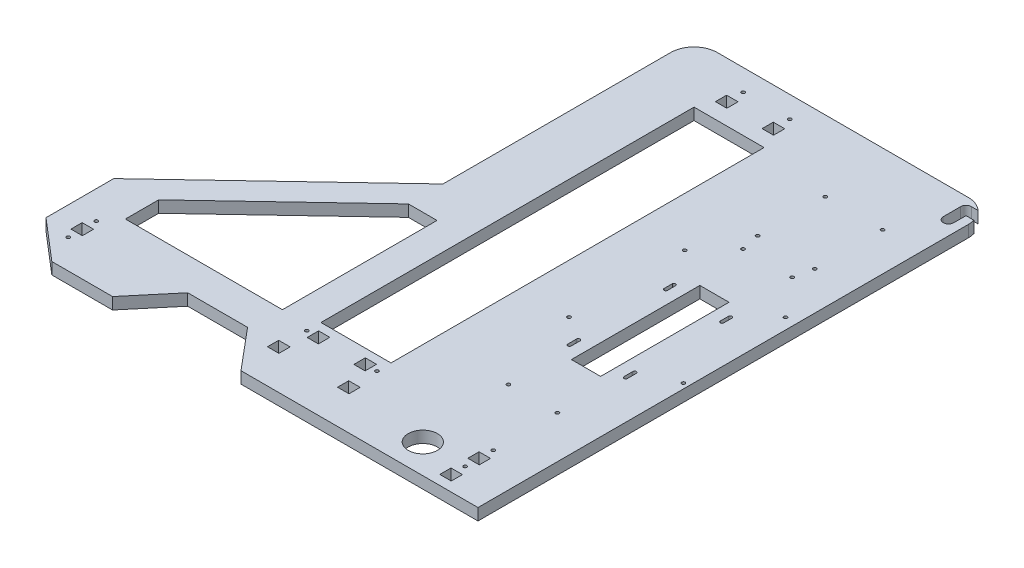
SolidWorks part; units mm, degrees
ref_plane "Front Plane" through (0, 0, 0) normal (0, 0, 1) x (1, 0, 0)
ref_plane "Top Plane" through (0, 0, 0) normal (0, 1, 0) x (1, 0, 0)
ref_plane "Right Plane" through (0, 0, 0) normal (1, 0, 0) x (0, 0, -1)
sketch "Sketch1" plane through (0, 0, 0) normal (0, 1, 0) x (1, 0, 0)
  line L0 (0, 0) -> (-235, 0)
  line L1 (-235, 0) -> (-235, -215)
  line L2 (-235, -215) -> (-380, -352)
  line L3 (-380, -352) -> (-380, -410)
  line L4 (-380, -410) -> (-345, -440)
  line L5 (-345, -440) -> (-293, -440)
  line L6 (-293, -440) -> (-263.6315, -405)
  line L7 (-263.6315, -405) -> (-212.3685, -405)
  line L8 (-212.3685, -405) -> (-183, -440)
  line L9 (-183, -440) -> (0, -440)
  line L10 (0, 0) -> (0, -440)
  line L12 (-293, -440) -> (-183, -440) construction
  dimension "D3" = 235
  dimension "D5" = 58
  dimension "D13" = 190
  dimension "D7" = 35
  dimension "D15" = 52
  dimension "D12" = 30
  dimension "D10" = 35
  dimension "D6" = 380
  dimension "D4" = 440
  dimension "D2" = 50
  dimension "D8" = 50
  dimension "D9" = 110
extrude "Boss-Extrude1" add sketch "Sketch1" along normal blind 10
sketch "Sketch16" plane through (0, 10, 0) normal (0, 1, 0) x (1, 0, 0)
  line L0 (0, -440) -> (20, -440)
  line L1 (20, -440) -> (20, 0)
  line L2 (20, 0) -> (0, 0)
  line L3 (0, 0) -> (0, -440)
  dimension "D1" = 20
  dimension "D2" = 90
extrude "Boss-Extrude2" add sketch "Sketch16" against normal through all
sketch "Sketch2" plane through (0, 10, 0) normal (0, 1, 0) x (1, 0, 0)
  line L0 (-235, -215) -> (-235, -405) construction
  line L1 (-263.6315, -405) -> (-212.3685, -405) construction
  line L2 (-345, -440) -> (-345, -318.931) construction
  line L3 (-235, -215) -> (-380, -352) construction
  line L4 (-345, -348.5097) -> (-235, -244.5787)
  line L5 (-235, -244.5787) -> (-210.5, -244.5787)
  line L6 (-210.5, -244.5787) -> (-210.5, -377)
  line L7 (-210.5, -377) -> (-345, -377)
  line L8 (-345, -377) -> (-345, -348.5097)
  line L9 (0, -440) -> (0, 0) construction
  line L10 (-184.5, -370) -> (-124.5, -370)
  line L11 (-184.5, -370) -> (-184.5, -50.45)
  line L12 (-184.5, -50.45) -> (-124.5, -50.45)
  line L13 (-124.5, -370) -> (-124.5, -50.45)
  line L14 (-124.5, -382.1) -> (-184.5, -382.1) construction
  line L15 (-16, -440) -> (-16, 0) construction
  line L16 (20, 0) -> (-235, 0) construction
  line L17 (-355.95, -430.6143) -> (-355.95, -329.2769) construction
  line L18 (-20.9, -431.8) -> (-11.1, -431.8)
  line L19 (-20.9, -431.8) -> (-20.9, -422.2)
  line L20 (-20.9, -422.2) -> (-11.1, -422.2)
  line L21 (-11.1, -431.8) -> (-11.1, -422.2)
  line L22 (-20.9, -431.8) -> (-11.1, -422.2) construction
  line L23 (-20.9, -422.2) -> (-11.1, -431.8) construction
  line L24 (-20.9, -407.8) -> (-11.1, -407.8)
  line L25 (-20.9, -407.8) -> (-20.9, -398.2)
  line L26 (-20.9, -398.2) -> (-11.1, -398.2)
  line L27 (-11.1, -407.8) -> (-11.1, -398.2)
  line L28 (-20.9, -407.8) -> (-11.1, -398.2) construction
  line L29 (-20.9, -398.2) -> (-11.1, -407.8) construction
  line L30 (-380, -410) -> (-345, -440) construction
  line L32 (-351.05, -398.2) -> (-360.85, -398.2)
  line L33 (-351.05, -398.2) -> (-351.05, -407.8)
  line L34 (-351.05, -407.8) -> (-360.85, -407.8)
  line L35 (-360.85, -398.2) -> (-360.85, -407.8)
  line L36 (-351.05, -398.2) -> (-360.85, -407.8) construction
  line L37 (-351.05, -407.8) -> (-360.85, -398.2) construction
  line L38 (-183, -440) -> (20, -440) construction
  line L39 (-183, -440) -> (20, -440) construction
  line L40 (-173.724, -32.45) -> (-113.724, -32.45) construction
  line L41 (-154.5, -50.45) -> (-154.5, -32.45) construction
  line L42 (-179.4, -27.65) -> (-169.6, -27.65)
  line L43 (-179.4, -27.65) -> (-179.4, -37.25)
  line L44 (-179.4, -37.25) -> (-169.6, -37.25)
  line L45 (-169.6, -27.65) -> (-169.6, -37.25)
  line L46 (-179.4, -27.65) -> (-169.6, -37.25) construction
  line L47 (-179.4, -37.25) -> (-169.6, -27.65) construction
  line L48 (-129.6, -37.25) -> (-139.4, -27.65) construction
  line L49 (-129.6, -27.65) -> (-139.4, -37.25) construction
  line L50 (-139.4, -27.65) -> (-139.4, -37.25)
  line L51 (-129.6, -37.25) -> (-139.4, -37.25)
  line L52 (-129.6, -27.65) -> (-129.6, -37.25)
  line L53 (-129.6, -27.65) -> (-139.4, -27.65)
  line L54 (-174.5, -32.45) -> (-174.5, -18.45) construction
  line L55 (-134.5, -32.45) -> (-134.5, -18.45) construction
  line L56 (-154.5, -370) -> (-154.5, -440) construction
  line L57 (-174.5, -382.1) -> (-134.5, -382.1) construction
  line L58 (-129.7, -387) -> (-139.3, -377.2) construction
  line L59 (-179.3, -377.2) -> (-169.7, -377.2)
  line L60 (-179.3, -377.2) -> (-179.3, -387)
  line L61 (-179.3, -387) -> (-169.7, -387)
  line L62 (-169.7, -377.2) -> (-169.7, -387)
  line L63 (-179.3, -377.2) -> (-169.7, -387) construction
  line L64 (-179.3, -387) -> (-169.7, -377.2) construction
  line L65 (-129.7, -377.2) -> (-139.3, -387) construction
  line L66 (-139.3, -377.2) -> (-139.3, -387)
  line L67 (-129.7, -387) -> (-139.3, -387)
  line L68 (-129.7, -377.2) -> (-129.7, -387)
  line L69 (-129.7, -377.2) -> (-139.3, -377.2)
  line L70 (-119.6, -410.9) -> (-129.4, -401.3) construction
  line L71 (-189.4, -401.3) -> (-179.6, -401.3)
  line L72 (-189.4, -401.3) -> (-189.4, -410.9)
  line L73 (-189.4, -410.9) -> (-179.6, -410.9)
  line L74 (-179.6, -401.3) -> (-179.6, -410.9)
  line L75 (-189.4, -401.3) -> (-179.6, -410.9) construction
  line L76 (-189.4, -410.9) -> (-179.6, -401.3) construction
  line L77 (-119.6, -401.3) -> (-129.4, -410.9) construction
  line L78 (-129.4, -401.3) -> (-129.4, -410.9)
  line L79 (-119.6, -410.9) -> (-129.4, -410.9)
  line L80 (-119.6, -401.3) -> (-119.6, -410.9)
  line L81 (-119.6, -401.3) -> (-129.4, -401.3)
  line L82 (-360.85, -398.2) -> (-11.1, -398.2) construction
  circle A0 centre (-16, -415) radius 1.45
  circle A1 centre (-16, -391) radius 1.45
  circle A2 centre (-355.95, -415) radius 1.45
  circle A3 centre (-355.95, -391) radius 1.45
  circle A4 centre (-174.5, -18.45) radius 1.45
  circle A5 centre (-134.5, -18.45) radius 1.45
  circle A6 centre (-124.5, -382.1) radius 1.45
  circle A7 centre (-184.5, -382.1) radius 1.45
  point P25 (-16, -427)
  point P30 (-16, -403)
  point P44 (-355.95, -403)
  point P61 (-174.5, -32.45)
  point P72 (-134.5, -32.45)
  point P85 (-174.5, -382.1)
  point P94 (-134.5, -382.1)
  point P95 (-184.5, -406.1)
  point P104 (-124.5, -406.1)
  point P105 (-154.5, -382.1)
  dimension "D13" = 2.9
  dimension "D14" = 2.9
  dimension "D23" = 2.9
  dimension "D24" = 2.9
  dimension "D31" = 2.9
  dimension "D37" = 2.9
  dimension "D1" = 21.5
  dimension "D2" = 28
  dimension "D3" = 24.5
  dimension "D4" = 60
  dimension "D7" = 26
  dimension "D8" = 9.6
  dimension "D9" = 9.8
  dimension "D10" = 9.8
  dimension "D11" = 9.6
  dimension "D12" = 24
  dimension "D15" = 24
  dimension "D19" = 9.8
  dimension "D20" = 9.6
  dimension "D26" = 12
  dimension "D27" = 9.8
  dimension "D28" = 9.6
  dimension "D33" = 9.6
  dimension "D38" = 9.8
  dimension "D39" = 9.6
  dimension "D41" = 24
  dimension "D34" = 30
  dimension "D36" = 12.1
  dimension "D30" = 18
  dimension "D29" = 40
  dimension "D17" = 13
  dimension "D32" = 14
  dimension "D35" = 20
  dimension "D16" = 12
  dimension "D21" = 90
  dimension "D25" = 24
  dimension "D5" = 349.75
  dimension "D22" = 349.75
  dimension "D40" = 30
  dimension "D6" = 70
  dimension "D42" = 0
  dimension "D43" = 0
  dimension "D18" = 16
  dimension "D44" = 9.8
extrude "Cut-Extrude1" cut sketch "Sketch2" against normal through all
fillet "Fillet1" radius 20 2 edges at (-235, 5, 0) (20, 5, 0)
sketch "Sketch11" plane through (0, 10, 0) normal (0, 1, 0) x (1, 0, 0)
  line L0 (-124.5, -210.225) -> (20, -210.225) construction
  line L1 (20, -440) -> (20, -20) construction
  line L3 (-52.25, -210.225) -> (-52.25, -440) construction
  line L6 (-124.5, -370) -> (-124.5, -50.45) construction
  line L8 (-183, -440) -> (20, -440) construction
  circle A0 centre (-52.25, -415) radius 12.5
  circle A1 centre (-16, -415) radius 1.45 construction
  dimension "D1" = 25
  dimension "D2" = 0
  dimension "D3" = 0
extrude "WiringHole" cut sketch "Sketch11" against normal through all
sketch "Sketch9" [suppressed] plane through (0, 10, 0) normal (0, 1, 0) x (1, 0, 0)
  line L0 (-52.25, -402.5) -> (-52.25, 0) construction
  line L1 (0, 0) -> (-215, 0) construction
  line L2 (-124.5, -205.225) -> (20, -205.225) construction
  line L3 (-124.5, -365) -> (-124.5, -45.45) construction
  line L4 (-4.75, -116.725) -> (-4.75, -293.725) construction
  line L6 (-99.75, -116.725) -> (-4.75, -116.725) construction
  line L7 (-4.75, -293.725) -> (-99.75, -293.725) construction
  line L8 (-99.75, -293.725) -> (-99.75, -116.725) construction
  line L9 (20, -440) -> (20, -20) construction
  circle A0 centre (-52.25, -415) radius 12.5 construction
  circle A1 centre (-99.75, -116.725) radius 1.45
  circle A2 centre (-4.75, -116.725) radius 1.45
  circle A3 centre (-4.75, -293.725) radius 1.45
  circle A4 centre (-99.75, -293.725) radius 1.45
  dimension "D3" = 2.9
  dimension "D4" = 2.9
  dimension "D1" = 95
  dimension "D2" = 177
  dimension "D5" = 47.5
extrude "MountingHoles-PSU" [suppressed] cut sketch "Sketch9" against normal through all
sketch "Sketch10" plane through (0, 10, 0) normal (0, 1, 0) x (1, 0, 0)
  line L0 (-124.5, -210.225) -> (20, -210.225) construction
  line L1 (20, -440) -> (20, -20) construction
  line L2 (-49.75, -235.225) -> (-24.75, -235.225) construction
  line L3 (-37.25, -210.225) -> (-37.25, 0) construction
  line L4 (-52.25, -210.225) -> (-52.25, -184.5972) construction
  line L7 (-124.5, -370) -> (-124.5, -50.45) construction
  line L8 (-49.75, -290.225) -> (-24.75, -290.225)
  line L9 (-49.75, -290.225) -> (-49.75, -180.225)
  line L10 (-49.75, -180.225) -> (-24.75, -180.225)
  line L11 (-24.75, -290.225) -> (-24.75, -180.225)
  line L12 (-49.75, -290.225) -> (-24.75, -180.225) construction
  line L13 (-49.75, -180.225) -> (-24.75, -290.225) construction
  line L15 (0, 0) -> (-215, 0) construction
  line L17 (-37.25, -210.225) -> (-37.25, -440) construction
  line L18 (-183, -440) -> (20, -440) construction
  line L19 (-64.75, -210.225) -> (-39.75, -210.225) construction
  line L20 (-37.25, -290.225) -> (-37.25, -180.225) construction
  dimension "D1" = 25
  dimension "D2" = 110
  dimension "D3" = 0
  dimension "D4" = 0
  dimension "D5" = 0
  dimension "D6" = 25
  dimension "D7" = 15
extrude "WiringSlot" cut sketch "Sketch10" against normal through all
sketch "CenterLines" plane through (0, 10, 0) normal (0, 1, 0) x (1, 0, 0)
  line L0 (-37.25, -290.225) -> (-37.25, -180.225) construction
  line L1 (-49.75, -290.225) -> (-24.75, -290.225) construction
  line L2 (-24.75, -180.225) -> (-49.75, -180.225) construction
  line L3 (-49.75, -235.225) -> (-24.75, -235.225) construction
  line L4 (-49.75, -180.225) -> (-49.75, -290.225) construction
  line L5 (-24.75, -290.225) -> (-24.75, -180.225) construction
ref_plane "Plane1" through (-37.25, 0, 0) normal (1, 0, 0) x (0, 0, -1)
sketch "Sketch6" plane through (0, 10, 0) normal (0, 1, 0) x (1, 0, 0)
  line L0 (-37.25, -290.225) -> (-37.25, -180.225) construction
  line L1 (-61.35, -235.225) -> (-13.15, -235.225) construction
  line L2 (-13.15, -190.775) -> (-13.15, -273.275) construction
  line L3 (-49.75, -290.225) -> (-24.75, -290.225) construction
  line L4 (-49.75, -235.225) -> (-24.75, -235.225) construction
  line L5 (-24.75, -180.225) -> (-49.75, -180.225) construction
  line L6 (-13.15, -190.775) -> (-13.15, -197.775) construction
  line L7 (-11.7, -190.775) -> (-11.7, -197.775)
  line L8 (-14.6, -190.775) -> (-14.6, -197.775)
  line L9 (-49.75, -235.225) -> (-24.75, -235.225) construction
  line L10 (-49.75, -180.225) -> (-49.75, -290.225) construction
  line L11 (-24.75, -290.225) -> (-24.75, -180.225) construction
  line L12 (-13.15, -280.275) -> (-13.15, -273.275) construction
  line L13 (-14.6, -280.275) -> (-14.6, -273.275)
  line L14 (-61.35, -272.675) -> (-61.35, -197.775) construction
  line L15 (-13.15, -280.275) -> (-13.15, -197.775) construction
  line L16 (-11.7, -280.275) -> (-11.7, -273.275)
  arc A2 (-11.7, -190.775) -> (-14.6, -190.775) centre (-13.15, -190.775) ccw
  arc A3 (-14.6, -197.775) -> (-11.7, -197.775) centre (-13.15, -197.775) ccw
  circle A4 centre (-61.35, -272.675) radius 1.45
  circle A6 centre (-61.35, -197.775) radius 1.45
  arc A8 (-14.6, -280.275) -> (-11.7, -280.275) centre (-13.15, -280.275) ccw
  arc A9 (-11.7, -273.275) -> (-14.6, -273.275) centre (-13.15, -273.275) ccw
  point P20 (-13.15, -194.275)
  point P25 (-13.15, -276.775)
  dimension "D6" = 0
  dimension "D8" = 2.9
  dimension "D12" = 2.9
  dimension "D4" = 1.45
  dimension "D5" = 1.45
  dimension "D11" = 82.5
  dimension "D14" = 74.9
  dimension "D2" = 24.1
  dimension "D3" = 48.2
  dimension "D9" = 7
  dimension "D10" = 7
extrude "MountingHoles-RAMPS" cut sketch "Sketch6" against normal through all
mirror "Mirror1" about plane through (-37.25, 0, 0) normal (1, 0, 0) of "MountingHoles-RAMPS"
sketch "Sketch5" plane through (0, 10, 0) normal (0, 1, 0) x (1, 0, 0)
  line L0 (-24.75, -235.225) -> (-49.75, -235.225) construction
  line L3 (-24.75, -290.225) -> (-24.75, -180.225) construction
  line L5 (-49.75, -180.225) -> (-49.75, -290.225) construction
  line L7 (-16.25, -134.725) -> (-58.25, -134.725) construction
  line L8 (-16.25, -335.725) -> (-58.25, -335.725) construction
  line L9 (-37.25, -235.225) -> (-37.25, -134.725) construction
  line L10 (-37.25, -235.225) -> (-37.25, -335.725) construction
  circle A0 centre (-58.25, -134.725) radius 1.45
  circle A1 centre (-16.25, -134.725) radius 1.45
  circle A2 centre (-16.25, -335.725) radius 1.45
  circle A3 centre (-58.25, -335.725) radius 1.45
  point P17 (-37.25, -134.725)
  point P22 (-37.25, -335.725)
  dimension "D2" = 2.9
  dimension "D5" = 2.9
  dimension "D6" = 2.9
  dimension "D7" = 2.9
  dimension "D3" = 201
  dimension "D4" = 100.5
  dimension "D8" = 21
  dimension "D9" = 21
  dimension "D10" = 100.5
extrude "MountingHoles-Melzi" cut sketch "Sketch5" against normal through all
sketch "Sketch13" plane through (0, 0, 0) normal (0, -1, 0) x (-1, 0, 0)
  line L0 (49.75, -210.225) -> (124.5, -210.225) construction
  line L1 (124.5, -370) -> (124.5, -50.45) construction
  line L2 (82.25, -259.74) -> (82.25, -160.71) construction
  line L3 (37.25, -290.225) -> (37.25, -180.225) construction
  line L4 (49.75, -180.225) -> (49.75, -290.225) construction
  line L6 (82.25, -259.74) -> (-15.65, -259.74) construction
  circle A0 centre (82.25, -160.71) radius 1.45
  circle A1 centre (82.25, -259.74) radius 1.45
  circle A2 centre (-10.59, -167.19) radius 1.45
  circle A3 centre (-15.65, -259.74) radius 1.45
  point P11 (82.25, -210.225)
  dimension "D8" = 2.9
  dimension "D6" = 2.9
  dimension "D1" = 2.9
  dimension "D2" = 49.515
  dimension "D3" = 45
  dimension "D4" = 6.48
  dimension "D5" = 92.84
  dimension "D7" = 97.9
extrude "Mountingholes-Smoothieboard" cut sketch "Sketch13" against normal through all
mirror "Flipped" [suppressed] about plane through (-37.25, 0, 0) normal (1, 0, 0)
sketch "Sketch21" plane through (0, 10, 0) normal (0, 1, 0) x (1, 0, 0)
  line L0 (-37.25, -180.225) -> (-37.25, 0) construction
  line L1 (-24.75, -180.225) -> (-49.75, -180.225) construction
  line L2 (0, 0) -> (-215, 0) construction
  line L3 (-37.25, -89.725) -> (-23.3697, -89.725) construction
  circle A0 centre (-12.75, -60.725) radius 1.45
  circle A1 centre (-61.75, -60.725) radius 1.45
  circle A2 centre (-61.75, -118.725) radius 1.45
  circle A3 centre (-12.75, -118.725) radius 1.45
  circle A4 centre (-16.25, -134.725) radius 1.45 construction
  dimension "D1" = 2.9
  dimension "D2" = 24.5
  dimension "D3" = 29
  dimension "D4" = 45
extrude "Pi" cut sketch "Sketch21" against normal through all
sketch "Sketch17" plane through (0, 10, 0) normal (0, 1, 0) x (1, 0, 0)
  line L0 (0, 0) -> (20, 0) construction
  line L1 (20, -23.6361) -> (20, 0) construction
  line L2 (20, -440) -> (20, -20) construction
  line L3 (20, -10) -> (8, -10) construction
  line L4 (20, -14.5) -> (8, -14.5)
  line L5 (20, -5.5) -> (8, -5.5)
  arc A0 (20, -14.5) -> (20, -5.5) centre (20, -10) ccw
  arc A1 (8, -5.5) -> (8, -14.5) centre (8, -10) ccw
  point P8 (14, -10)
  dimension "D1" = 9
  dimension "D2" = 12
  dimension "D3" = 10
extrude "Cut-Extrude3" cut sketch "Sketch17" against normal through all
sketch "Sketch18" plane through (0, 10, 0) normal (0, 1, 0) x (1, 0, 0)
  line L0 (8, -5.5) -> (8, -14.5) construction
  line L1 (3.5, -10) -> (8, -10) construction
  line L2 (8, -10) -> (8, -25) construction
  line L3 (12.5, -10) -> (12.5, -25)
  line L4 (3.5, -10) -> (3.5, -25)
  arc A0 (8, -5.5) -> (8, -14.5) centre (8, -10) ccw construction
  arc A1 (12.5, -10) -> (3.5, -10) centre (8, -10) ccw
  arc A2 (3.5, -25) -> (12.5, -25) centre (8, -25) ccw
  point P10 (8, -17.5)
  dimension "D1" = 9
  dimension "D2" = 0
  dimension "D3" = 15
extrude "Cut-Extrude4" cut sketch "Sketch18" against normal through all
sketch "Sketch19" plane through (0, 10, 0) normal (0, 1, 0) x (1, 0, 0)
  line L0 (-2, -25) -> (18, -25) construction
  line L1 (8, -25) -> (8, -5.5) construction
  circle A0 centre (18, -25) radius 1.45
  arc A1 (8, -5.5) -> (3.5, -10) centre (8, -10) ccw construction
  circle A2 centre (-2, -25) radius 1.45
  dimension "D2" = 2.9
extrude "Cut-Extrude5" [suppressed] cut sketch "Sketch19" against normal through all
equation "\"Y-ROD-SPACING\"=75"
equation "\"Y-BED-OFFSET\"=2"
equation "\"Y-BED-ROD-INSET\"=3.5"
equation "\"T-SLOT-NUT-FILLET-RADIUS\"=0.5"
equation "\"T-SLOT-SCREW-SHAFT-RADIUS\"=1.55"
equation "\"T-SLOT-SCREW-SHAFT-CUTOUT-LENGTH\"=11"
equation "\"T-SLOT-NUT-DEPTH\"=3.5"
equation "\"T-SLOT-NUT-WIDTH\"=2.85"
equation "\"T-SLOT-NUT-END-DISTANCE\"=8"
equation "\"ACRYLIC-TAB-CUTOUT-SIZE\"=\"ACRYLIC-THICKNESS\"+\"ACRYLIC-TAB-TOLERANCE\"*2"
equation "\"ACRYLIC-TAB-WIDTH\"=\"ACRYLIC-THICKNESS\""
equation "\"ACRYLIC-M3-HOLE\"=2.9"
equation "\"SMOOTHROD-CAP-SCREW-DISTANCE\"=20"
equation "\"FRAME-WIDTH-INNER\"=370"
equation "\"D24@Sketch2\"=\"ACRYLIC-M3-HOLE\""
equation "\"D23@Sketch2\"=\"ACRYLIC-M3-HOLE\""
equation "\"D19@Sketch2\"=\"ACRYLIC-THICKNESS\"-\"KERF\"*2"
equation "\"D20@Sketch2\"=\"ACRYLIC-TAB-WIDTH\"-\"KERF\"*4"
equation "\"D37@Sketch2\"=\"ACRYLIC-M3-HOLE\""
equation "\"D33@Sketch2\"=\"ACRYLIC-TAB-WIDTH\"-\"KERF\"*4"
equation "\"D38@Sketch2\"=\"ACRYLIC-THICKNESS\"-\"KERF\"*2"
equation "\"D39@Sketch2\"=\"ACRYLIC-TAB-WIDTH\"-\"KERF\"*4"
equation "\"D13@Sketch2\"=\"ACRYLIC-M3-HOLE\""
equation "\"D14@Sketch2\"=\"ACRYLIC-M3-HOLE\""
equation "\"D8@Sketch2\"=\"ACRYLIC-TAB-WIDTH\"-\"KERF\"*4"
equation "\"D9@Sketch2\"=\"ACRYLIC-THICKNESS\"-\"KERF\"*2"
equation "\"D10@Sketch2\"=\"ACRYLIC-THICKNESS\"-\"KERF\"*2"
equation "\"D11@Sketch2\"=\"ACRYLIC-TAB-WIDTH\"-\"KERF\"*4"
equation "\"D31@Sketch2\"=\"ACRYLIC-M3-HOLE\""
equation "\"D27@Sketch2\"=\"ACRYLIC-THICKNESS\"-\"KERF\"*2"
equation "\"D28@Sketch2\"=\"ACRYLIC-TAB-WIDTH\"-\"KERF\"*4"
equation "\"NEMA17-HOLE-SPACING\"=31"
equation "\"NEMA17-CENTRAL-CUTOUT\"=22.5"
equation "\"Z-BRACKET-REACH\"=55"
equation "\"TOP-BRACKET-SPACING\"=40"
equation "\"D29@Sketch2\"=\"TOP-BRACKET-SPACING\""
equation "\"ACRYLIC-THICKNESS\"=10"
equation "\"SMOOTHROD-Z-LENGTH\"=350"
equation "\"D5@Sketch2\"=\"SMOOTHROD-Z-LENGTH\"-\"SMOOTHROD-TIGHTENING-HEADROOM\""
equation "\"SMOOTHROD-X-LENGTH\"=350"
equation "\"SMOOTHROD-Y-LENGTH\"=350"
equation "\"D22@Sketch2\"=\"SMOOTHROD-Y-LENGTH\"-\"SMOOTHROD-TIGHTENING-HEADROOM\""
equation "\"SMOOTHROD-TIGHTENING-HEADROOM\"=.25"
equation "\"X-ROD-SPACING\"=45"
equation "\"Z-ROD-SPACING\"=17.5"
equation "\"LEADSCREW-Z-LENGTH\"=300"
equation "\"SCREW-HEAD-RADIUS\"=6"
equation "\"PRINTED-X-SMOOTHROD-DIAMETER\"=9.0"
equation "\"PRINTED-X-SMOOTHROD-CUTOUT\"=10"
equation "\"PRINTED-X-BASE-HEIGHT\"=10"
equation "\"PRINTED-LM8UU-CUTOUT-SIZE\"=15.5"
equation "\"PRINTED-LM8UU-CUTOUT-LENGTH\"=24.5"
equation "\"PRINTED-X-IDLER-HEIGHT\"=16"
equation "\"PSU-MOUNTING-WIDTH\"=95"
equation "\"PSU-MOUNTING-HEIGHT\"=177"
equation "\"D1@Sketch9\"=\"PSU-MOUNTING-WIDTH\""
equation "\"D3@Sketch9\"=\"ACRYLIC-M3-HOLE\""
equation "\"D1@Boss-Extrude1\"=\"ACRYLIC-THICKNESS\""
equation "\"D6@Sketch1\"=\"SMOOTHROD-Y-LENGTH\"+30"
equation "\"D4@Sketch9\"=\"ACRYLIC-M3-HOLE\""
equation "\"D2@Sketch9\"=\"PSU-MOUNTING-HEIGHT\""
equation "\"D5@Sketch9\"=\"PSU-MOUNTING-WIDTH\"/2"
equation "\"D4@Sketch1\"=\"SMOOTHROD-Z-LENGTH\"+90"
equation "\"D8@Sketch6\"=\"ACRYLIC-M3-HOLE\""
equation "\"D12@Sketch6\"=\"ACRYLIC-M3-HOLE\""
equation "\"D2@Sketch5\"=\"ACRYLIC-M3-HOLE\""
equation "\"D5@Sketch5\"=\"ACRYLIC-M3-HOLE\""
equation "\"D6@Sketch5\"=\"ACRYLIC-M3-HOLE\""
equation "\"D7@Sketch5\"=\"ACRYLIC-M3-HOLE\""
equation "\"D1@Sketch13\"=\"ACRYLIC-M3-HOLE\""
equation "\"D6@Sketch13\"=\"ACRYLIC-M3-HOLE\""
equation "\"D8@Sketch13\"=\"ACRYLIC-M3-HOLE\""
equation "\"D4@Sketch6\"=\"ACRYLIC-M3-HOLE\"/2"
equation "\"D5@Sketch6\"=\"ACRYLIC-M3-HOLE\"/2"
equation "\"Y-BED-SCREW-SPACING\"=209"
equation "\"Y-BED-SCREW-CUTOUT-SLOT-HEIGHT\"=2"
equation "\"ACRYLIC-THICKNESS2\"=4.5"
equation "\"ACRYLIC-TAB-TOLERANCE\"=-.05"
equation "\"Z-ROD-INSET\"=13.5"
equation "\"SCREW-LENGTH-FRAME\"=\"ACRYLIC-THICKNESS\" + 10"
equation "\"SCREW-LENGTH-MOTOR\"=\"ACRYLIC-THICKNESS\" + 5"
equation "\"SCREW-LENGTH-EXTRUDER\"=28"
equation "\"Y-BELT-TO-ROD-DISTANCE\"=20"
equation "\"SPOOL-HOLDER-ROD-SPACING\"=150"
equation "\"ACRYLIC-X-CARRIAGE-WIDTH\"=55"
equation "\"ACRYLIC-X-CARRIAGE-HEIGHT\"=75"
equation "\"ACRYLIC-X-CARRIAGE-LM8UU-CUTOUT-WIDTH\"=24.25"
equation "\"ACRYLIC-X-CARRIAGE-SCREW-SPACING-X\"=15"
equation "\"ACRYLIC-X-CARRIAGE-SCREW-SPACING-Y\"=33"
equation "\"ACRYLIC-X-CARRIAGE-CENTER-TAB-SPACING\"=14"
equation "\"ACRYLIC-X-CARRIAGE-EXTRUDER-OFFSET\"=26"
equation "\"ACRYLIC-X-CARRIAGE-EXTRUDER-ANGLE\"=90"
equation "\"ACRYLIC-X-CARRIAGE-EXTRUDER-SHELF-DEPTH\"=\"ACRYLIC-X-CARRIAGE-EXTRUDER-OFFSET\" + 28"
equation "\"ACRYLIC-X-CARRIAGE-EXTRUDER-BRACE-SPACING\"=23"
equation "\"ACRYLIC-X-CARRIAGE-EXTRUDER-BRACE-TAB-OFFSET\"=20"
equation "\"ACRYLIC-X-CARRIAGE-EXTRUDER-BRACE-HEIGHT\"=35"
equation "\"ACRYLIC-X-CARRIAGE-EXTRUDER-BRACE-SCREW-SPACING\"=22"
equation "\"D1@Sketch19\"=\"SMOOTHROD-CAP-SCREW-DISTANCE\"/2"
equation "\"D2@Sketch19\"=\"ACRYLIC-M3-HOLE\""
equation "\"D1@Sketch21\"=\"ACRYLIC-M3-HOLE\""
equation "\"KERF\"=0.1"
equation "\"PRINTED-M3-HOLE\"=3.5"
equation "\"PRINTED-M3-NUT-AF\"=6.25"
equation "\"ACRYLIC-X-CARRIAGE-LM8UU-CUTOUT-HEIGHT\"=11.0"
equation "\"ACRYLIC-X-CARRIAGE-DUAL-WIDTH-MULTIPLIER\"=1.65"
equation "\"ACRYLIC-X-CARRIAGE-DUAL-HOTEND-SPACING\"=42"
equation "\"ACRYLIC-X-CARRIAGE-DUAL-WIDTH\"=75"
equation "\"ACRYLIC-X-CARRIAGE-DUAL-FAN-OFFSET\"=52"
equation "\"ACRYLIC-X-CARRIAGE-DUAL-FAN-HEIGHT\"=20"
equation "\"ACRYLIC-X-CARRIAGE-DUAL-HOTEND-SEPARATION\"=36"
equation "\"ACRYLIC-X-CARRIAGE-DUAL-MOUNT-PLATE-DEPTH\"=75"
equation "\"ACRYLIC-X-CARRIAGE-DUAL-MOUNT-BRACE-WIDTH\"=33"
equation "\"ACRYLIC-X-CARRIAGE-DUAL-MOUNT-SCREW-WIDTH\"=40"
equation "\"BLOWER-FAN-WIDTH\"=15"
equation "\"D44@Sketch2\"=\"ACRYLIC-THICKNESS\"-\"KERF\"*2"
